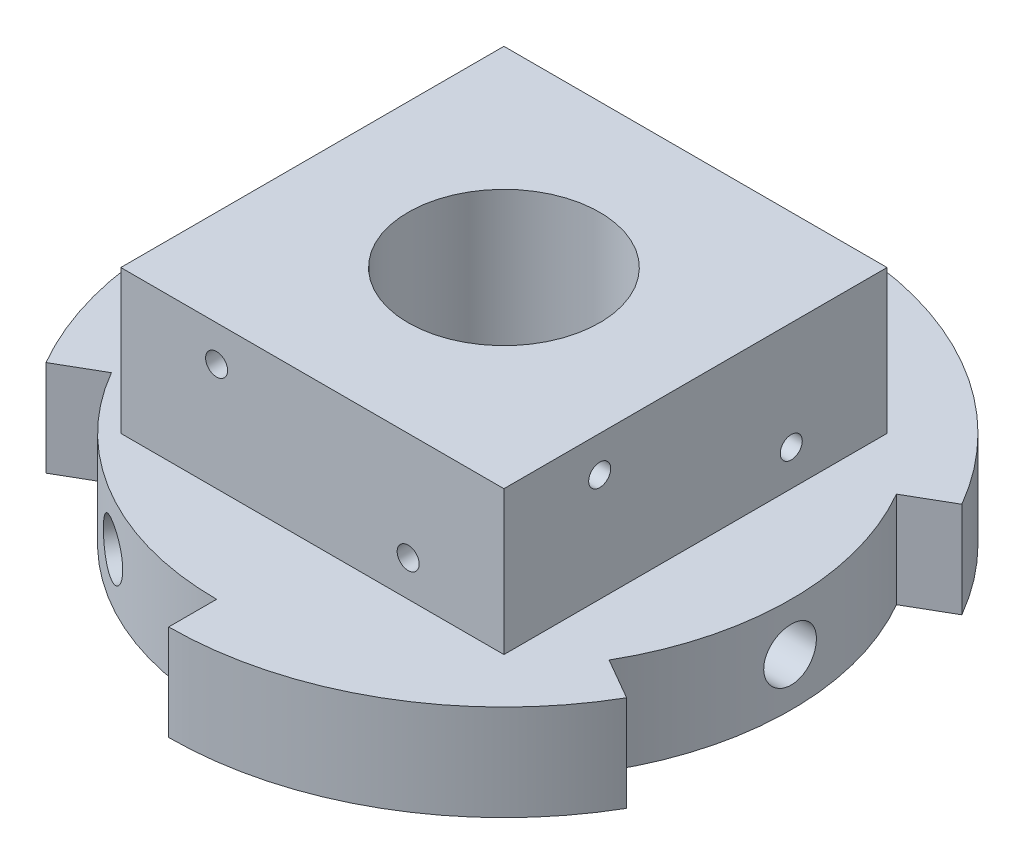
SolidWorks part; units mm, degrees
ref_plane "Front Plane" through (0, 0, 0) normal (0, 0, 1) x (1, 0, 0)
ref_plane "Top Plane" through (0, 0, 0) normal (0, 1, 0) x (1, 0, 0)
ref_plane "Right Plane" through (0, 0, 0) normal (1, 0, 0) x (0, 0, -1)
sketch "Sketch1" plane through (0, 0, 0) normal (0, 1, 0) x (1, 0, 0)
  line L0 (-30.3109, 17.5) -> (-25.9808, 15)
  line L1 (-30.3109, -17.5) -> (-25.9808, -15)
  line L2 (-30.3109, 17.5) -> (0, 0) construction
  line L3 (0, 0) -> (-30.3109, -17.5) construction
  line L4 (-0.4058, 0) -> (-50000.4058, 0) construction
  line L5 (30.3109, 17.5) -> (25.9808, 15)
  line L6 (0, 35) -> (0, 30)
  line L7 (0, -35) -> (0, -30)
  line L8 (30.3109, -17.5) -> (25.9808, -15)
  arc A1 (-30.3109, 17.5) -> (-30.3109, -17.5) centre (0, 0) ccw
  arc A3 (30.3109, 17.5) -> (0, 35) centre (0, 0) ccw
  circle A4 centre (0, 0) radius 30
  arc A5 (0, -35) -> (30.3109, -17.5) centre (0, 0) ccw
  point P1 (-30.3109, 17.5)
  point P5 (-35, 0)
  point P8 (0, 0)
  point P9 (33.8353, -19.5348)
  point P10 (0, 0)
  point P23 (0, 0)
  dimension "D1" = 35
  dimension "D5" = 60
  dimension "D2" = 5
  dimension "D3" = 60
  dimension "D4" = 3
extrude "Boss-Extrude3" add sketch "Sketch1" along normal blind 10 contours A4 L0 A1 L1 | A4 | A4 L5 A3 L6 | L7 A5 L8 A4 region at (-31.0964, 0, 0) region at (0, 0, 0) region at (15.5482, 0, -26.9303) region at (15.5482, 0, 26.9303)
ref_plane "Plane1" through (40, 0, 0) normal (1, 0, 0) x (0, 0, -1)
sketch "Sketch2" plane through (40, 0, 0) normal (1, 0, 0) x (0, 0, -1)
  line L0 (-15, 10) -> (15, 0) construction
  line L1 (15, 10) -> (-15, 0) construction
  circle A0 centre (0, 5) radius 2.75
  point P12 (15, 10)
  point P13 (15, 0)
  dimension "D1" = 5.5
extrude "Cut-Extrude1" cut sketch "Sketch2" against normal blind 25
pattern_circular "CirPattern1" count 3 over 360 about axis through (0, 10, 0) along (0, -1, 0) of "Cut-Extrude1"
sketch "Sketch3" plane through (0, 10, 0) normal (0, 1, 0) x (1, 0, 0)
  line L1 (20, -20) -> (-20, -20)
  line L2 (20, -20) -> (20, 20)
  line L3 (20, 20) -> (-20, 20)
  line L4 (-20, -20) -> (-20, 20)
  line L5 (20, -20) -> (-20, 20) construction
  line L6 (20, 20) -> (-20, -20) construction
  point P0 (0, 0)
  dimension "D1" = 40
  dimension "D2" = 40
extrude "Boss-Extrude4" add sketch "Sketch3" along normal blind 15
sketch "Sketch4" plane through (20, 0, 0) normal (1, 0, 0) x (0, 0, -1)
  line L0 (0, 25) -> (0, 10) construction
  line L1 (-20, 25) -> (20, 25) construction
  line L2 (-20, 10) -> (20, 10) construction
  line L3 (10, 10) -> (10, 13.75) construction
  line L4 (10, 10) -> (20, 10) construction
  line L7 (-10, 25) -> (-10, 21.25) construction
  line L8 (10, 25) -> (10, 25.0788) construction
  circle A0 centre (-10, 21.25) radius 1.15
  circle A1 centre (10, 13.75) radius 1.15
  point P11 (-10, 23.125)
  dimension "D1" = 2.3
  dimension "D2" = 2.3
  dimension "D3" = 10
  dimension "D4" = 20
  dimension "D5" = 3.75
  dimension "D6" = 3.75
sketch "Sketch5" plane through (0, 25, 0) normal (0, 1, 0) x (1, 0, 0)
  circle A0 centre (0, 0) radius 10
  dimension "D1" = 20
extrude "Cut-Extrude5" cut sketch "Sketch5" against normal through all
extrude "Cut-Extrude6" cut sketch "Sketch4" against normal blind 6 contours A0 | A1
pattern_circular "CirPattern2" count 4 over 360 about axis through (0, 0, 0) along (0, 1, 0) of "Cut-Extrude6" reverse direction yes
